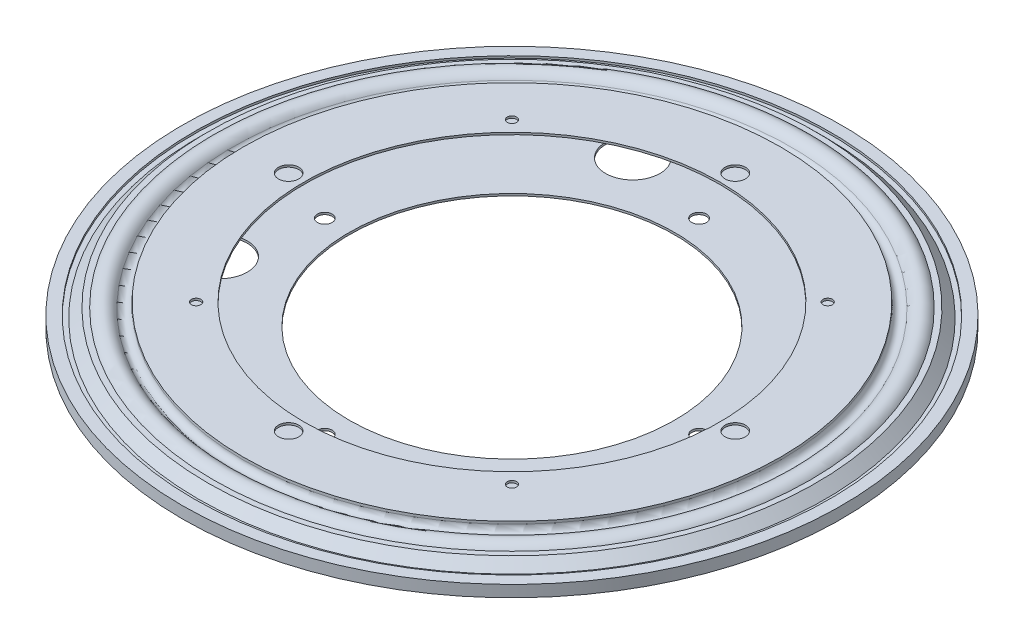
SolidWorks part; units mm, degrees
note: The reader was unsure of these and kept them because the rebuilt part matched: shared geometry of "Sketch1<7>".
ref_plane "Front" through (0, 0, 0) normal (0, 0, 1) x (1, 0, 0)
ref_plane "Top" through (0, 0, 0) normal (0, 1, 0) x (1, 0, 0)
ref_plane "Right" through (0, 0, 0) normal (1, 0, 0) x (0, 0, -1)
sketch "Sketch1" plane through (0, 0, 0) normal (0, 0, 1) x (1, 0, 0)
  line L0 (0, 21.7127) -> (0, -25.7345) construction
  line L1 (101.6, 7.2103) -> (101.6, -7.2103) construction
  line L2 (94.3641, -3.175) -> (94.3641, -4.064)
  line L3 (94.3641, 3.175) -> (94.3641, 4.064)
  line L4 (108.8359, -3.175) -> (108.8359, -4.064)
  line L5 (108.8359, -4.064) -> (115.7605, -4.064)
  line L6 (-2.2827, 0) -> (4.7936, 0) construction
  line L7 (94.3641, 4.064) -> (73.025, 4.064)
  line L8 (115.7605, -4.064) -> (115.7605, 0)
  line L9 (94.3641, -4.064) -> (57.15, -4.064)
  line L10 (87.3679, 0) -> (115.8321, 0) construction
  line L11 (115.7605, 0) -> (111.6965, 0)
  line L12 (113.7285, -0.889) -> (110.0857, -0.889)
  line L13 (110.0857, -0.889) -> (106.8039, 2.3928)
  line L14 (106.8039, 2.3928) -> (104.8849, 2.3928)
  arc A0 (98.1307, -2.1167) -> (94.3641, -3.175) centre (96.3961, -3.175) ccw
  arc A1 (98.1307, -2.1167) -> (105.0693, -2.1167) centre (101.6, 0) ccw
  arc A2 (105.0693, -2.1167) -> (108.8359, -3.175) centre (106.8039, -3.175) cw
  circle A3 centre (101.6, 0) radius 4.064 construction
  arc A4 (98.1307, 2.1167) -> (104.8849, 2.3928) centre (101.6, 0) cw
  arc A6 (98.1307, 2.1167) -> (94.3641, 3.175) centre (96.3961, 3.175) cw
  point P34 (113.7285, 0)
  dimension "D5" = 8.128
  dimension "D7" = 4.064
  dimension "D1" = 114.3
  dimension "D3" = 203.2
  dimension "D4" = 146.05
  dimension "D6" = 8.128
  dimension "D8" = 3.175
  dimension "D9" = 4.064
  dimension "D10" = 0.889
  dimension "D11" = 1.905
  dimension "D12" = 135
revolve "Revolve-Thin1" add sketch "Sketch1" angle 360 about L0
revolve "Revolve-Thin2" add sketch "Sketch1<7>" angle 360 about L0
sketch "Sketch1<7>" plane through (0, 0, 0) normal (0, 0, 1) x (1, 0, 0) same geometry as "Sketch1"
sketch "Sketch2" plane through (0, 0, 0) normal (0, 0, 1) x (1, 0, 0)
  line L0 (101.6, 7.2103) -> (101.6, -7.2103) construction
  line L1 (101.6, 3.2766) -> (101.6, -3.2766)
  line L2 (101.6, 5.3554) -> (101.6, -5.2305) construction
  line L3 (109.5725, -3.3274) -> (-109.5725, -3.3274) construction
  arc A0 (101.6, 3.2766) -> (101.6, -3.2766) centre (101.6, 0) cw
  circle A1 centre (101.6, 0) radius 4.064 construction
  dimension "D1" = 0.0508
revolve "Revolve1" add sketch "Sketch2" angle 360 about L2
pattern_circular "CirPattern1" count 9 over 360 about axis through (0, 0, 0) along (0, 1, 0) of bodies 128
sketch "Sketch3" plane through (0, -3.3274, 0) normal (0, 1, 0) x (-1, 0, 0)
  line L0 (0, 0) -> (0, -83.4152) construction
  line L1 (0, 0) -> (30.0159, -72.4647) construction
  line L2 (-15.4403, -6.3956) -> (15.4403, 6.3956) construction
  circle A0 centre (30.0159, -72.4647) radius 9.525
  circle A1 centre (-72.4647, -30.0159) radius 9.525
  circle A2 centre (-30.0159, 72.4647) radius 9.525
  circle A3 centre (72.4647, 30.0159) radius 9.525
  dimension "D1" = 19.05
  dimension "D3" = 156.8704
  dimension "D2" = 22.5
extrude "Cut-Extrude1" cut sketch "Sketch3" against normal through all
hole_wizard "9/32 (0.281250) Diameter Hole1" positions "Sketch5" profile "Sketch4" hole size "9/32" standard "Ansi Inch" end condition up to next
sketch "Sketch5" plane through (0, 4.064, 0) normal (0, 1, 0) x (-1, 0, 0)
  line L0 (19.7529, 0) -> (-13.4622, 0) construction
  point P0 (0, -78.4352)
  dimension "D1" = 156.8704
sketch "Sketch4" plane through (0, 4.064, -78.4352) normal (1, 0, 0) x (0, 0, 1)
  line L0 (0, 0) -> (0, 0.7376)
  line L1 (0, 0.7376) -> (3.5719, 0.7376)
  line L2 (3.5719, 0.7376) -> (3.5719, 0)
  line L5 (3.5719, 0) -> (0, 0)
  line L11 (0, -6.35) -> (0, 107.95) construction
  dimension "Thru Hole Dia." = 7.1437
  dimension "Thru Hole Depth" = 0.7376
pattern_circular "CirPattern2" count 4 over 360 about axis through (0, 0, 0) along (0, 1, 0) of "9/32 (0.281250) Diameter Hole1"
hole_wizard "13/64 (0.203130) Diameter Hole1" positions "Sketch7" profile "Sketch6" hole size "13/64" standard "Ansi Inch"
sketch "Sketch7" plane through (0, -3.3274, 0) normal (0, 1, 0) x (-1, 0, 0)
  line L0 (8.178, 0) -> (-7.4231, 0) construction
  point P0 (0, -65.7352)
  dimension "D1" = 131.4704
sketch "Sketch6" plane through (0, -3.3274, -65.7352) normal (1, 0, 0) x (0, 0, 1)
  line L0 (0, 0) -> (0, 9.6781)
  line L1 (0, 9.6781) -> (2.5798, 8.128)
  line L2 (2.5798, 8.128) -> (2.5798, 0)
  line L5 (2.5798, 0) -> (0, 0)
  line L10 (0, 9.6781) -> (-2.5798, 8.128) construction
  line L11 (0, -6.35) -> (0, 107.95) construction
  dimension "Hole Dia." = 5.1595
  dimension "Hole Depth" = 8.128
  dimension "Drill Angle" = 118
pattern_circular "CirPattern3" count 4 over 360 about axis through (0, 0, 0) along (0, 1, 0) of "13/64 (0.203130) Diameter Hole1"
hole_wizard "#97 (0.005900) Diameter Hole1" positions "Sketch9" profile "Sketch8" hole size "#97" standard "Ansi Inch" end condition up to next
sketch "Sketch9" plane through (0, 4.064, 0) normal (0, 1, 0) x (-1, 0, 0)
  line L0 (0, 0) -> (55.4621, 55.4621) construction
  line L1 (-9.5024, 9.5024) -> (9.5024, -9.5024) construction
  line L2 (0, 0) -> (0, 39.9168) construction
  point P0 (55.4621, 55.4621)
  dimension "D1" = 45
  dimension "D2" = 156.8704
sketch "Sketch8" plane through (-55.4621, 4.064, 55.4621) normal (1, 0, 0) x (0, 0, 1)
  line L0 (0, 0) -> (0, 0.7376)
  line L1 (0, 0.7376) -> (1.651, 0.7376)
  line L2 (1.651, 0.7376) -> (1.651, 0)
  line L5 (1.651, 0) -> (0, 0)
  line L11 (0, -6.35) -> (0, 107.95) construction
  dimension "Thru Hole Dia." = 3.302
  dimension "Thru Hole Depth" = 0.7376
pattern_circular "CirPattern4" count 4 over 360 about axis through (0, 0, 0) along (0, 1, 0) of "#97 (0.005900) Diameter Hole1"
equation "\"D7@Sketch1\"=\"D5@Sketch1\"/2"
